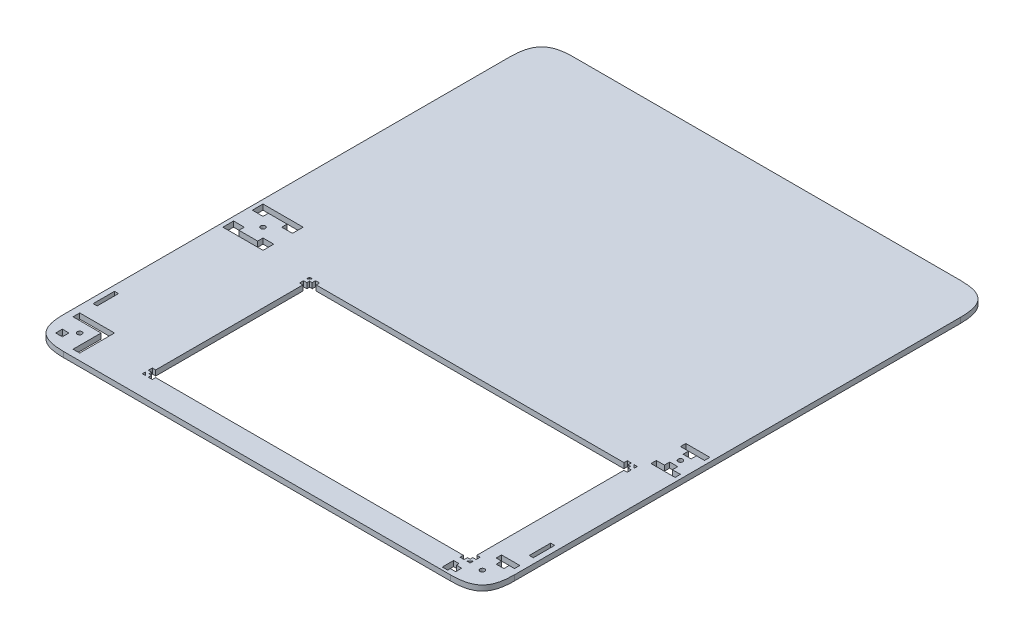
SolidWorks part; units mm, degrees
ref_plane "Front Plane" through (0, 0, 0) normal (0, 0, 1) x (1, 0, 0)
ref_plane "Top Plane" through (0, 0, 0) normal (0, 1, 0) x (1, 0, 0)
ref_plane "Right Plane" through (0, 0, 0) normal (1, 0, 0) x (0, 0, -1)
sketch "Sketch1" plane through (0, 0, 0) normal (0, 1, 0) x (1, 0, 0)
  line L1 (0, 0) -> (337, 0)
  line L2 (0, 0) -> (0, 381.22)
  line L3 (0, 381.22) -> (337, 381.22)
  line L4 (337, 0) -> (337, 381.22)
  line L5 (70.28, 137.5) -> (310.28, 137.5)
  line L6 (70.28, 137.5) -> (70.28, 17.5)
  line L7 (70.28, 17.5) -> (310.28, 17.5)
  line L8 (310.28, 137.5) -> (310.28, 17.5)
  dimension "D1" = 337
  dimension "D2" = 381.22
  dimension "D3" = 240
  dimension "D4" = 120
  dimension "D5" = 17.5
  dimension "D6" = 26.72
extrude "Boss-Extrude1" add sketch "Sketch1" against normal blind 4
fillet "Fillet1" radius 24 4 edges at (0, -2, 0) (337, -2, 0) (0, -2, -381.22) (337, -2, -381.22) conic rho 0.55
sketch "Sketch3" plane through (0, 0, 0) normal (0, 1, 0) x (1, 0, 0)
  line L0 (337, 24) -> (337, 357.22) construction
  line L1 (24, 0) -> (313, 0) construction
  line L2 (0, 357.22) -> (0, 24) construction
  line L3 (309, 4) -> (309, 2)
  line L4 (305, 10.5) -> (309, 10.5)
  line L5 (305, 10.5) -> (305, 2)
  line L6 (305, 2) -> (309, 2)
  line L7 (309, 10.5) -> (309, 8.5)
  line L8 (309, 8.5) -> (313, 8.5)
  line L10 (309, 4) -> (313, 4)
  line L11 (313, 8.5) -> (313, 4)
  line L12 (329, 28) -> (333, 28)
  line L13 (319.28, 32) -> (333, 32)
  line L14 (319.28, 32) -> (319.28, 28)
  line L15 (319.28, 28) -> (323.28, 28)
  line L16 (333, 32) -> (333, 28)
  line L18 (323.28, 28) -> (323.28, 24)
  line L19 (323.28, 24) -> (329, 24)
  line L20 (329, 28) -> (329, 24)
  line L21 (328, 151) -> (334, 151)
  line L30 (26, 5) -> (31, 5)
  line L36 (26, 5) -> (26, 26)
  line L37 (9, 14) -> (14, 14)
  line L38 (9, 14) -> (9, 9)
  line L39 (9, 9) -> (14, 9)
  line L40 (14, 14) -> (14, 9)
  line L41 (26, 31) -> (31, 31)
  line L42 (31, 5) -> (31, 31)
  line L43 (26, 31) -> (5, 31)
  line L45 (26, 26) -> (5, 26)
  line L46 (5, 31) -> (5, 26)
  line L47 (3, 140) -> (33, 140)
  line L48 (3, 140) -> (3, 144)
  line L49 (11, 144) -> (25, 144)
  line L50 (33, 140) -> (33, 144)
  line L52 (3, 144) -> (3, 148)
  line L53 (3, 148) -> (11, 148)
  line L54 (11, 144) -> (11, 148)
  line L56 (33, 144) -> (33, 148)
  line L57 (33, 148) -> (25, 148)
  line L58 (25, 144) -> (25, 148)
  line L59 (3, 170) -> (33, 170)
  line L60 (3, 170) -> (3, 166)
  line L61 (11, 166) -> (25, 166)
  line L62 (33, 170) -> (33, 166)
  line L64 (3, 166) -> (3, 162)
  line L65 (3, 162) -> (11, 162)
  line L66 (11, 166) -> (11, 162)
  line L68 (33, 166) -> (33, 162)
  line L69 (33, 162) -> (25, 162)
  line L70 (25, 166) -> (25, 162)
  line L71 (316, 147) -> (334, 147)
  line L72 (316, 147) -> (316, 151)
  line L73 (316, 151) -> (322, 151)
  line L74 (334, 147) -> (334, 151)
  line L76 (322, 151) -> (322, 155)
  line L77 (322, 155) -> (328, 155)
  line L78 (328, 151) -> (328, 155)
  line L79 (328, 169) -> (334, 169)
  line L80 (316, 173) -> (334, 173)
  line L81 (316, 173) -> (316, 169)
  line L82 (316, 169) -> (322, 169)
  line L83 (334, 173) -> (334, 169)
  line L85 (322, 169) -> (322, 165)
  line L86 (322, 165) -> (328, 165)
  line L87 (328, 169) -> (328, 165)
  line L89 (333, 42) -> (330, 42)
  line L90 (333, 42) -> (333, 58)
  line L91 (333, 58) -> (330, 58)
  line L92 (330, 42) -> (330, 58)
  line L93 (4, 42) -> (7, 42)
  line L94 (4, 42) -> (4, 58)
  line L95 (4, 58) -> (7, 58)
  line L96 (7, 42) -> (7, 58)
  circle A0 centre (322, 15) radius 1.75
  circle A1 centre (18, 18) radius 1.75
  circle A2 centre (18, 155) radius 1.75
  circle A3 centre (325, 160) radius 1.75
  point P37 (5, 28.5)
  dimension "D3" = 3.5
  dimension "D6" = 3.5
  dimension "D45" = 3.5
  dimension "D62" = 3.5
  dimension "D1" = 15
  dimension "D2" = 15
  dimension "D4" = 18
  dimension "D5" = 18
  dimension "D7" = 24
  dimension "D8" = 4
  dimension "D9" = 2
  dimension "D10" = 2
  dimension "D11" = 4.5
  dimension "D12" = 2
  dimension "D13" = 4
  dimension "D14" = 4
  dimension "D15" = 13.72
  dimension "D16" = 4
  dimension "D17" = 4
  dimension "D18" = 4
  dimension "D19" = 4
  dimension "D20" = 24
  dimension "D21" = 5
  dimension "D22" = 5
  dimension "D23" = 9
  dimension "D24" = 9
  dimension "D25" = 26
  dimension "D26" = 5
  dimension "D27" = 5
  dimension "D28" = 5
  dimension "D29" = 21
  dimension "D30" = 5
  dimension "D31" = 30
  dimension "D32" = 4
  dimension "D33" = 4
  dimension "D34" = 8
  dimension "D35" = 8
  dimension "D36" = 4
  dimension "D37" = 30
  dimension "D38" = 4
  dimension "D39" = 4
  dimension "D40" = 4
  dimension "D41" = 30
  dimension "D42" = 140
  dimension "D43" = 3
  dimension "D44" = 3
  dimension "D46" = 11
  dimension "D47" = 4
  dimension "D48" = 4
  dimension "D49" = 4
  dimension "D50" = 18
  dimension "D51" = 3
  dimension "D52" = 6
  dimension "D53" = 6
  dimension "D54" = 4
  dimension "D55" = 4
  dimension "D56" = 4
  dimension "D57" = 18
  dimension "D58" = 6
  dimension "D59" = 6
  dimension "D60" = 10
  dimension "D61" = 147
  dimension "D63" = 5
  dimension "D64" = 9
  dimension "D65" = 3
  dimension "D66" = 16
  dimension "D67" = 10
  dimension "D68" = 4
  dimension "D69" = 4
  dimension "D70" = 16
  dimension "D71" = 3
  dimension "D72" = 0
extrude "Cut-Extrude1" cut sketch "Sketch3" against normal up to next
ref_plane "Plane3" through (190.28, 0, 0) normal (-1, 0, 0) x (0, 0, 1)
ref_plane "Plane6" through (0, 0, -77.5) normal (0, 0, 1) x (1, 0, 0)
sketch "Sketch5" plane through (0, 0, 0) normal (0, 1, 0) x (1, 0, 0)
  line L0 (310.28, 17.5) -> (310.28, 137.5) construction
  line L3 (310.28, 15) -> (312.78, 15)
  line L4 (312.78, 17.5) -> (312.78, 15)
  line L5 (310.28, 22.5) -> (312.78, 22.5)
  line L6 (310.28, 22.5) -> (310.28, 19.5)
  line L7 (310.28, 19.5) -> (312.78, 19.5)
  line L8 (312.78, 22.5) -> (312.78, 19.5)
  line L9 (70.28, 17.5) -> (310.28, 17.5) construction
  line L10 (305.28, 17.5) -> (308.28, 17.5)
  line L11 (305.28, 17.5) -> (305.28, 15)
  line L12 (305.28, 15) -> (308.28, 15)
  line L13 (308.28, 17.5) -> (308.28, 15)
  line L14 (310.28, 15) -> (312.78, 17.5)
  dimension "D1" = 2.5
  dimension "D2" = 2.5
  dimension "D4" = 3
  dimension "D6" = 3
extrude "Cut-Extrude2" cut sketch "Sketch5" against normal up to next
mirror "Mirror1" about plane through (0, 0, -77.5) normal (0, 0, 1) of "Cut-Extrude2" second plane through (190.28, 0, 0) second plane normal (-1, 0, 0)
